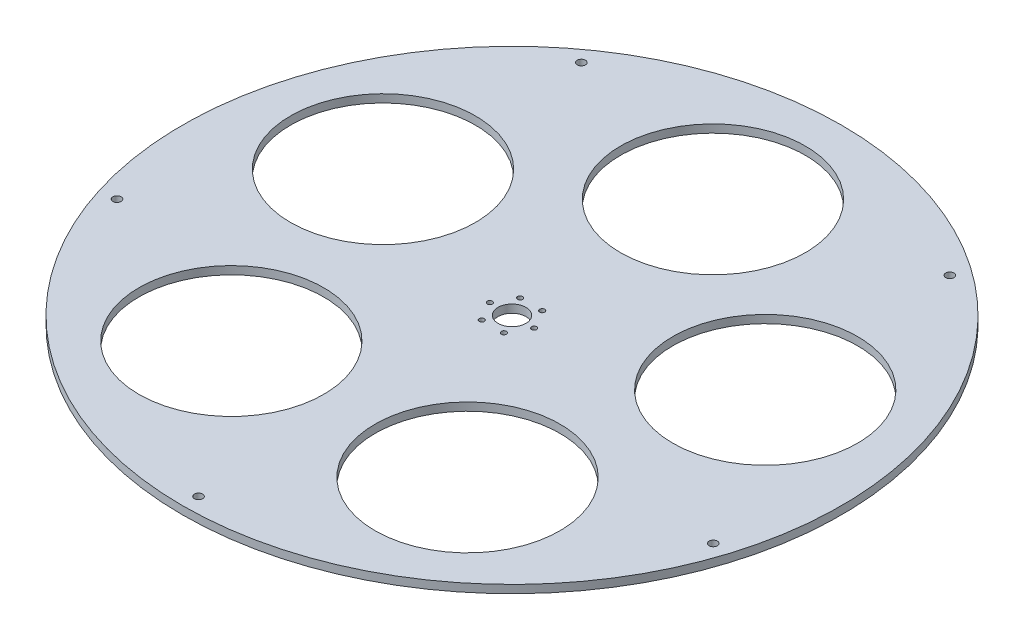
SolidWorks part; units mm, degrees
material "PC High Viscosity"
ref_plane "Front Plane" through (0, 0, 0) normal (0, 0, 1) x (1, 0, 0)
ref_plane "Top Plane" through (0, 0, 0) normal (0, 1, 0) x (1, 0, 0)
ref_plane "Right Plane" through (0, 0, 0) normal (1, 0, 0) x (0, 0, -1)
sketch "Sketch1" plane through (0, 0, 0) normal (0, 1, 0) x (1, 0, 0)
  circle A0 centre (0, 0) radius 260.35
  circle A1 centre (0, 158.75) radius 73.025
  circle A2 centre (150.9802, 49.0564) radius 73.025
  circle A3 centre (93.3109, -128.4314) radius 73.025
  circle A4 centre (-93.3109, -128.4314) radius 73.025
  circle A5 centre (-150.9802, 49.0564) radius 73.025
  point P15 (0, 0)
  dimension "D1" = 520.7
  dimension "D2" = 146.05
  dimension "D3" = 158.75
  dimension "D4" = 5
extrude "Boss-Extrude1" add sketch "Sketch1" along normal blind 6.35
sketch "Sketch3" plane through (-5.1845, 6.35, -2.4486) normal (0, 1, 0) x (1, 0, 0)
  circle A0 centre (5.1845, -2.4486) radius 11
  circle A1 centre (5.1845, -2.4486) radius 260.35 construction
  point P3 (0, 0)
  point P4 (0, 0)
  point P6 (0, 0)
  point P7 (0, 0)
  dimension "D1" = 22
extrude "Cut-Extrude1" cut sketch "Sketch3" against normal through all
hole_wizard "#10-32 Tapped Hole1" positions "Sketch5" profile "Sketch7" tap size "#10-32" standard "ANSI Inch" end condition through all
sketch "Sketch5" plane through (-5.1845, 6.35, -2.4486) normal (0, 1, 0) x (1, 0, 0)
  line L0 (5.1845, -2.4486) -> (-3.5467, 12.6744) construction
  line L2 (5.1845, -2.4486) -> (5.1845, 15.0139) construction
  circle A0 centre (5.1845, -2.4486) radius 17.4625
  point P0 (-3.5467, 12.6744)
  point P22 (13.9158, 12.6744)
  point P23 (22.647, -2.4486)
  point P24 (13.9158, -17.5715)
  point P25 (-3.5467, -17.5715)
  point P26 (-12.278, -2.4486)
  dimension "D1" = 34.925
  dimension "D2" = 30
  dimension "D3" = 6
sketch "Sketch7" plane through (-8.7313, 6.35, -15.123) normal (1, 0, 0) x (0, 0, 1)
  line L0 (0, 0) -> (0, 6.35)
  line L1 (0, 6.35) -> (2.0193, 6.35)
  line L2 (2.0193, 6.35) -> (2.0193, 0)
  line L5 (2.0193, 0) -> (0, 0)
  line L11 (0, -6.35) -> (0, 107.95) construction
  dimension "Thru Tap Drill Dia." = 4.0386
  dimension "Thru Tap Drill Depth" = 6.35
cosmetic thread "Hole Thread1" parameters "D2"=4.826
cosmetic thread "Hole Thread2" parameters "D2"=4.826
cosmetic thread "Hole Thread3" parameters "D2"=4.826
cosmetic thread "Hole Thread4" parameters "D2"=4.826
cosmetic thread "Hole Thread5" parameters "D2"=4.826
cosmetic thread "Hole Thread6" parameters "D2"=4.826
sketch "Sketch8" plane through (0, 6.35, 0) normal (0, 1, 0) x (1, 0, 0)
  circle A0 centre (0, -247.65) radius 3.2512
  circle A1 centre (-235.5291, -76.5281) radius 3.2512
  circle A2 centre (-145.565, 200.3531) radius 3.2512
  circle A3 centre (145.565, 200.3531) radius 3.2512
  circle A4 centre (235.5291, -76.5281) radius 3.2512
  point P14 (0, 0)
  dimension "D2" = 6.5024
  dimension "D1" = 247.65
  dimension "D3" = 5
extrude "Cut-Extrude2" cut sketch "Sketch8" against normal through all
